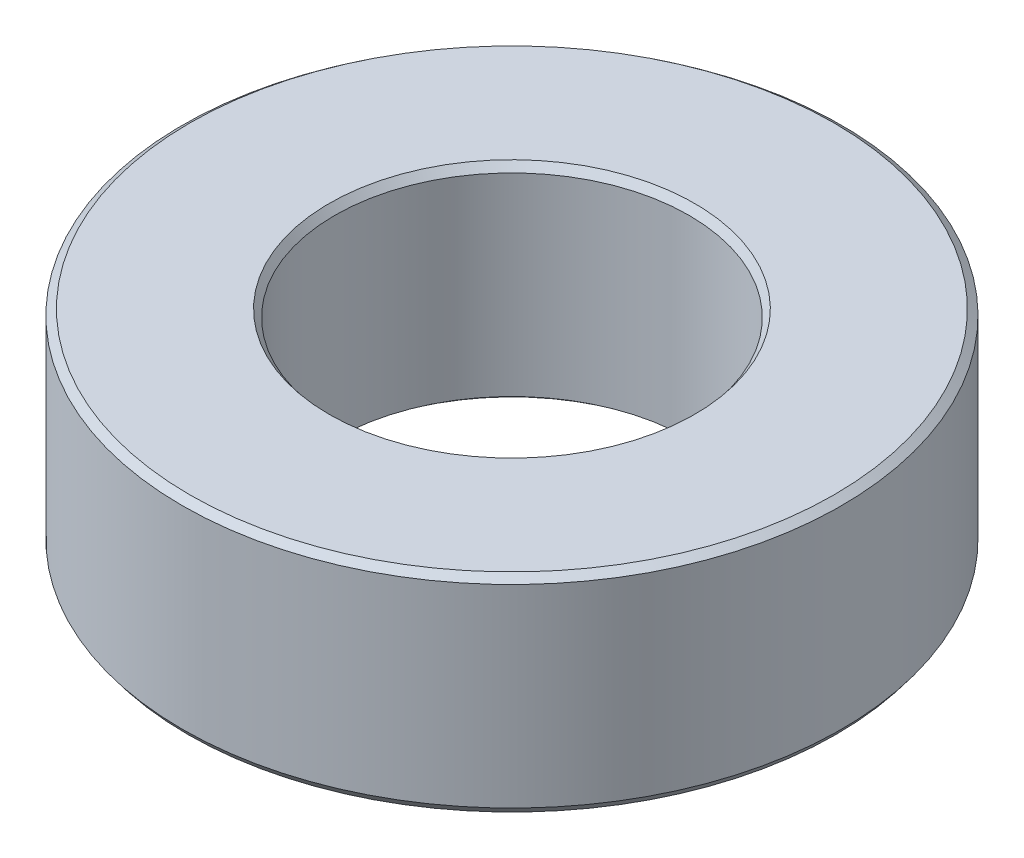
SolidWorks part; units mm, degrees
ref_plane "Front Plane" through (0, 0, 0) normal (0, 0, 1) x (1, 0, 0)
ref_plane "Top Plane" through (0, 0, 0) normal (0, 1, 0) x (1, 0, 0)
ref_plane "Right Plane" through (0, 0, 0) normal (1, 0, 0) x (0, 0, -1)
sketch "Sketch1" plane through (0, 0, 0) normal (0, 1, 0) x (1, 0, 0)
  circle A0 centre (0, 0) radius 57.5
  dimension "SLEEVE_OD" = 115
extrude "Boss-Extrude1" add sketch "Sketch1" along normal blind 36.0684
sketch "Sketch2" plane through (0, 0, 0) normal (0, 1, 0) x (1, 0, 0)
  circle A0 centre (0, 0) radius 30.897
  dimension "BORE_D" = 61.7939
extrude "Cut-Extrude1" cut sketch "Sketch2" along normal through all
chamfer "Chamfer1" distance 0.9871 angle 52.861 4 edges at (0, 36.0684, 30.897) (0, 0, 30.897) (0, 0, 57.5) (0, 36.0684, 57.5) first distance on face at (0, 36.0684, 30.897) first distance on face at (0, 0, 30.897) first distance on face at (0, 36.0684, 57.5)
